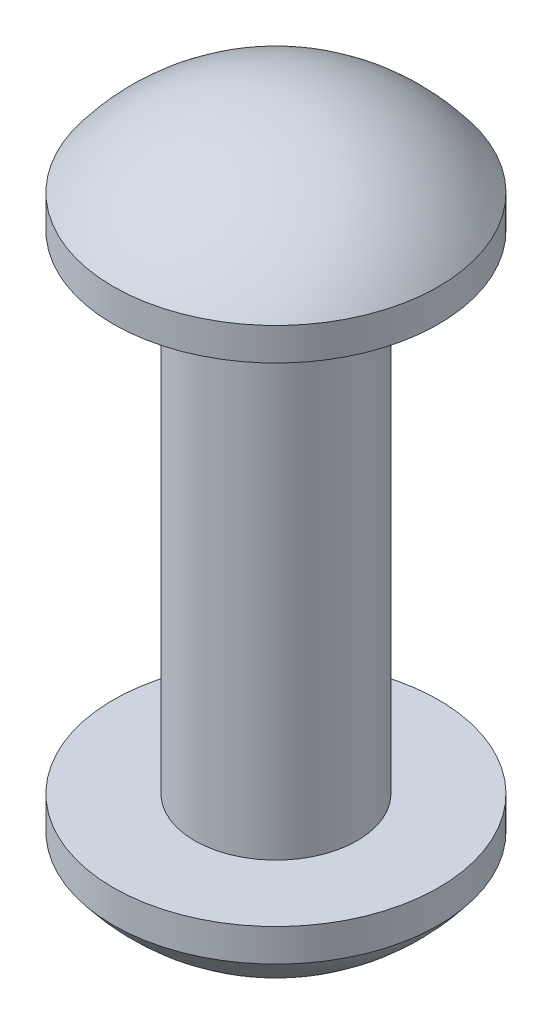
SolidWorks part; units mm, degrees
material "Латунь"
ref_plane "Спереди" through (0, 0, 0) normal (0, 0, 1) x (1, 0, 0)
ref_plane "Сверху" through (0, 0, 0) normal (0, 1, 0) x (1, 0, 0)
ref_plane "Справа" through (0, 0, 0) normal (1, 0, 0) x (0, 0, -1)
sketch "Эскиз1" plane through (0, 0, 0) normal (0, 1, 0) x (1, 0, 0)
  circle A0 centre (0, 0) radius 3
  dimension "D1" = 6
extrude "Бобышка-Вытянуть1" add sketch "Эскиз1" along normal mid plane 18
sketch "Эскиз2" plane through (0, 9, 0) normal (0, 1, 0) x (1, 0, 0)
  circle A2 centre (0, 0) radius 6
  circle A3 centre (0, 0) radius 6
  dimension "D1" = 3
extrude "Бобышка-Вытянуть2" add sketch "Эскиз2" along normal blind 1.2
dome "Купол1" faces to dome 1 distance 3 reverse direction no elliptical dome no face at (0, 10.2, 6) parameters "D1"=3
mirror "Зеркальное отражение1" about plane through (0, 0, 0) normal (0, 1, 0) of "Купол1", "Бобышка-Вытянуть2"
equation "\"длина лезвия\"=900"
equation "\"радиус острия\"=3"
equation "\"длина острия\"=40"
equation "\"ширина лезвия\"=20"
equation "\"радиус сгиба\"=2"
equation "\"высота ребра жесткости\"=7"
equation "\"толщина лезвия \"=2"
equation "\"длина рукоятки\"=200"
equation "\"тлщина рукоятки\"=30"
equation "\"диаметр заклепки\"=6"
equation "\"расстояние между заклнпками\"=75"
equation "\"глубина заклепки\"=6"
equation "\"отступ от заклепки\"=3"
equation "\"диаметр шляпы\"=\"диаметр заклепки\" + 2*\"отступ от заклепки\""
equation "\"радиус скруглений\"=5"
equation "\"D1@Эскиз1\"=\"диаметр заклепки\""
equation "\"D1@Эскиз2\"=\"отступ от заклепки\""
equation "\"высота головки\"=1.2"
equation "\"высота купола\"=3"
equation "\"D1@Бобышка-Вытянуть2\"=\"высота головки\""
equation "\"D1@Купол1\"=\"высота купола\""
equation "\"D1@Бобышка-Вытянуть1\"=\"тлщина рукоятки\" - 2 * \"глубина заклепки\""
